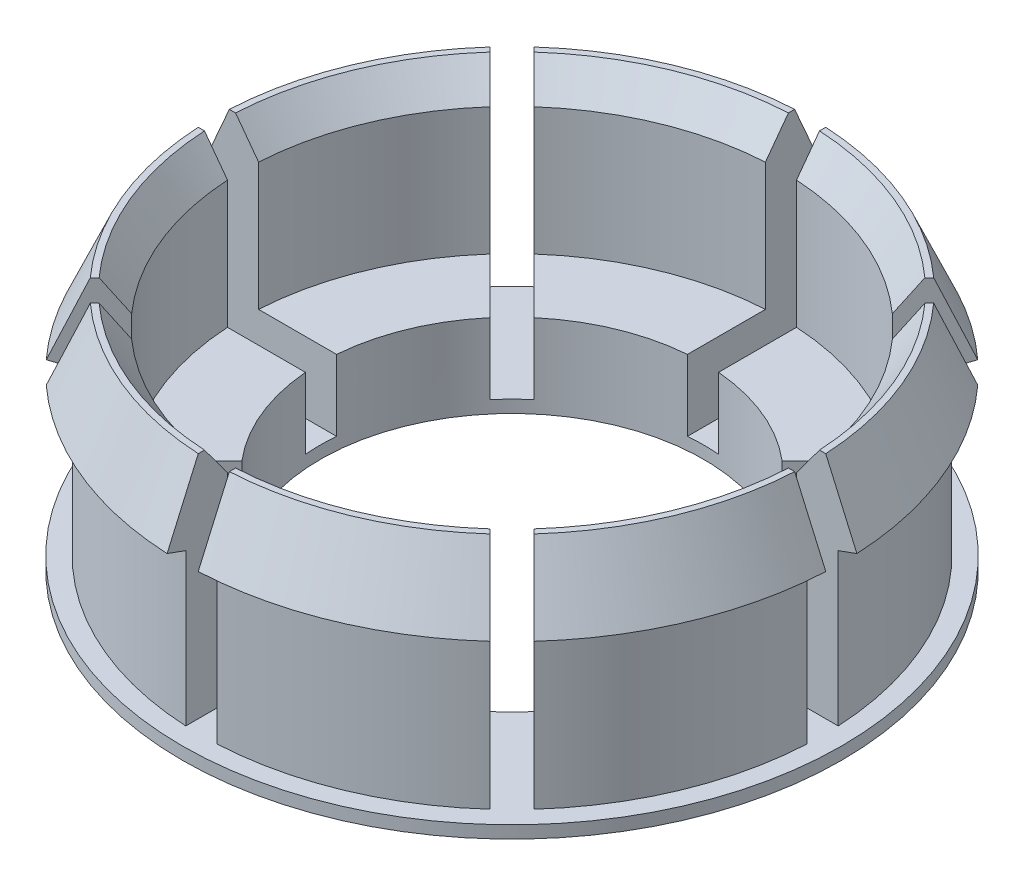
SolidWorks part; units mm, degrees
ref_plane "Front Plane" through (0, 0, 0) normal (0, 0, 1) x (1, 0, 0)
ref_plane "Top Plane" through (0, 0, 0) normal (0, 1, 0) x (1, 0, 0)
ref_plane "Right Plane" through (0, 0, 0) normal (1, 0, 0) x (0, 0, -1)
sketch "Sketch5" plane through (0, 0, 0) normal (0, 0, 1) x (1, 0, 0)
  line L0 (-11, -3.2385) -> (-11, 1.9685)
  line L1 (11, 3.2385) -> (-11, 3.2385) construction
  line L2 (11, 3.2385) -> (11, -3.2385) construction
  line L3 (11, -3.2385) -> (-11, -3.2385) construction
  line L4 (-11, 1.9685) -> (-11, -3.2385) construction
  line L5 (11, 3.2385) -> (-11, -3.2385) construction
  line L6 (11, -3.2385) -> (-11, 3.2385) construction
  line L7 (-11.938, 3.2385) -> (-12.192, 3.2385)
  line L8 (-12.192, 3.2385) -> (-13.462, 0.3408)
  line L9 (-13.462, 0.3408) -> (-12.7, 0.0635)
  line L10 (-12.7, 0.0635) -> (-12.7, -6.1365)
  line L11 (-12.7, -6.1365) -> (-13.462, -6.1365)
  line L12 (-13.462, -6.1365) -> (-13.462, -6.6445)
  line L13 (-13.462, -6.6445) -> (-7.825, -6.6445)
  line L14 (-7.825, -6.6445) -> (-7.825, -3.2385)
  line L15 (-7.825, -3.2385) -> (-11, -3.2385)
  line L16 (0, 0.0635) -> (0, -8.827) construction
  line L17 (7.825, -6.6445) -> (-7.825, -6.6445) construction
  line L18 (7.825, -6.6445) -> (7.825, -3.2385) construction
  line L19 (7.825, -3.2385) -> (-7.825, -3.2385) construction
  line L20 (-7.825, -6.6445) -> (-7.825, -3.2385) construction
  line L21 (7.825, -6.6445) -> (-7.825, -3.2385) construction
  line L22 (7.825, -3.2385) -> (-7.825, -6.6445) construction
  line L23 (12.7, -6.1365) -> (-12.7, -6.1365) construction
  line L24 (12.7, -6.1365) -> (12.7, 0.0635) construction
  line L25 (12.7, 0.0635) -> (-12.7, 0.0635) construction
  line L26 (-12.7, -6.1365) -> (-12.7, 0.0635) construction
  line L27 (12.7, -6.1365) -> (-12.7, 0.0635) construction
  line L28 (12.7, 0.0635) -> (-12.7, -6.1365) construction
  line L29 (-11.938, 3.2385) -> (-11, 1.9685)
  line L30 (11, 3.7615) -> (-11, 3.7615) construction
  line L31 (11, 3.7615) -> (11, -3.2385) construction
  line L32 (11, -3.2385) -> (-11, -3.2385) construction
  line L33 (-11, 3.7615) -> (-11, 3.2385) construction
  line L34 (11, 3.7615) -> (-11, -3.2385) construction
  line L35 (11, -3.2385) -> (-11, 3.7615) construction
  line L36 (-11, 1.9685) -> (-11, 3.2385) construction
  line L37 (-11, 3.2385) -> (-11, 1.9685) construction
  line L38 (-11, 3.2385) -> (-11, 1.9685) construction
  line L39 (-11, 1.9685) -> (-11, -3.2385) construction
  line L40 (-11, 3.2385) -> (-11.938, 3.2385) construction
  point P0 (0, 0)
  point P7 (0, -4.9415)
  point P15 (0, 0.2615)
  point P19 (0, -3.0365)
  dimension "D2" = 22
  dimension "D4" = 6.2
  dimension "D6" = 25.4
  dimension "D7" = 0.762
  dimension "D8" = 1.27
  dimension "D9" = 0.508
  dimension "D3" = 3.175
  dimension "D10" = 0.762
  dimension "D5" = 3.175
  dimension "D11" = 70
  dimension "D12" = 3.302
  dimension "D13" = 7
  dimension "D14" = 1.27
  dimension "D15" = 0.254
revolve "Revolve1" add sketch "Sketch5" angle 360 about L16
sketch "Sketch6" plane through (0, 3.2385, 0) normal (0, 1, 0) x (1, 0, 0)
  line L1 (0.635, 0) -> (-0.635, 0)
  line L2 (0.635, 0) -> (0.635, 13.462)
  line L3 (0.635, 13.462) -> (-0.635, 13.462)
  line L4 (-0.635, 0) -> (-0.635, 13.462)
  line L5 (0.635, 0) -> (-0.635, 13.462) construction
  line L6 (0.635, 13.462) -> (-0.635, 0) construction
  circle A0 centre (0, 0) radius 13.462 construction
  point P0 (0, 6.731)
  dimension "D1" = 1.27
extrude "Cut-Extrude3" cut sketch "Sketch6" against normal up to surface (9.375 mm away) and the other way through all up to face at (0, -6.1365, 13.462)
ref_axis "Axis1" through (0, 4.0728, 0) along (0, -1, 0)
pattern_circular "CirPattern1" count 8 over 360 about axis through (0, 4.0728, 0) along (0, -1, 0) of "Cut-Extrude3"
equation "\"D4@Sketch5\"=6.2mm"
